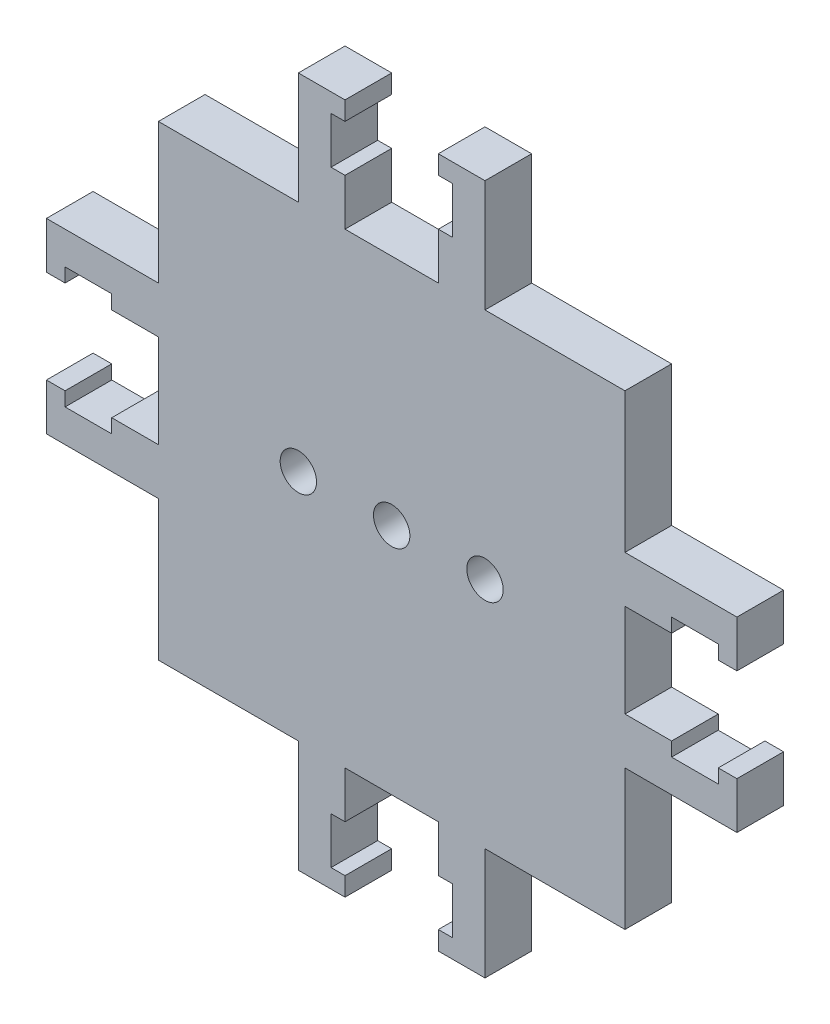
SolidWorks part; units mm, degrees
ref_plane "Plan de face" through (0, 0, 0) normal (0, 0, 1) x (1, 0, 0)
ref_plane "Plan de dessus" through (0, 0, 0) normal (0, 1, 0) x (1, 0, 0)
ref_plane "Plan de droite" through (0, 0, 0) normal (1, 0, 0) x (0, 0, -1)
sketch "Esquisse1" plane through (0, 0, 0) normal (0, 0, 1) x (1, 0, 0)
  line L0 (0, -10.9037) -> (0, 0) construction
  line L1 (0, 0) -> (78.1485, 0) construction
  line L2 (-25, 25) -> (-10, 25)
  line L3 (0, 0) -> (90.4553, 90.4553) construction
  line L4 (10, 25) -> (25, 25)
  line L5 (-25, -25) -> (-10, -25)
  line L6 (25, -25) -> (25, -10)
  line L8 (25, 10) -> (25, 25)
  line L9 (-25, -25) -> (-25, -10)
  line L10 (-25, 10) -> (-25, 25)
  line L13 (10, -25) -> (25, -25)
  circle A0 centre (0, 0) radius 1.95
  circle A1 centre (10, 0) radius 1.95
  circle A2 centre (-10, 0) radius 1.95
  line B0 (0, -25) -> (0, -13.135) construction
  line B1 (0, -25) -> (-5, -25)
  line B2 (-5, -30) -> (-10, -30) construction
  line B3 (-10, -30) -> (-10, -25)
  line B4 (-5, -30) -> (-5, -25)
  line B5 (0, -25) -> (5, -25)
  line B6 (5, -25) -> (5, -30)
  line B7 (5, -30) -> (10, -30) construction
  line B8 (10, -30) -> (10, -25)
  line B9 (-10, -30) -> (-10, -37)
  line B10 (-10, -37) -> (-5, -37)
  line B11 (-5, -37) -> (-5, -35)
  line B12 (-5, -35) -> (-6.5, -35)
  line B13 (-6.5, -35) -> (-6.5, -30)
  line B14 (-6.5, -30) -> (-5, -30)
  line B15 (5, -35) -> (6.5, -35)
  line B16 (10, -37) -> (5, -37)
  line B17 (5, -37) -> (5, -35)
  line B18 (6.5, -35) -> (6.5, -30)
  line B19 (10, -30) -> (10, -37)
  line B20 (10, -30) -> (10, -25)
  line B21 (5, -30) -> (6.5, -30)
  line B22 (0, -25) -> (0, -13.135) construction
  line B23 (0, -25) -> (5, -25)
  line B24 (5, -30) -> (10, -30) construction
  line B25 (10, -30) -> (10, -25)
  line B26 (5, -30) -> (5, -25)
  line B27 (0, -25) -> (-5, -25)
  line B28 (-5, -25) -> (-5, -30)
  line B29 (-5, -30) -> (-10, -30) construction
  line B30 (-10, -30) -> (-10, -25)
  line B31 (10, -30) -> (10, -37)
  line B32 (10, -37) -> (5, -37)
  line B33 (5, -37) -> (5, -35)
  line B34 (5, -35) -> (6.5, -35)
  line B35 (6.5, -35) -> (6.5, -30)
  line B36 (6.5, -30) -> (5, -30)
  line B37 (-5, -35) -> (-6.5, -35)
  line B38 (-10, -37) -> (-5, -37)
  line B39 (-5, -37) -> (-5, -35)
  line B40 (-6.5, -35) -> (-6.5, -30)
  line B41 (-10, -30) -> (-10, -37)
  line B42 (-10, -30) -> (-10, -25)
  line B43 (-5, -30) -> (-6.5, -30)
  line B44 (0, 25) -> (0, 13.135) construction
  line B45 (0, 25) -> (-5, 25)
  line B46 (-5, 30) -> (-10, 30) construction
  line B47 (-10, 30) -> (-10, 25)
  line B48 (-5, 30) -> (-5, 25)
  line B49 (0, 25) -> (5, 25)
  line B50 (5, 25) -> (5, 30)
  line B51 (5, 30) -> (10, 30) construction
  line B52 (10, 30) -> (10, 25)
  line B53 (-10, 30) -> (-10, 37)
  line B54 (-10, 37) -> (-5, 37)
  line B55 (-5, 37) -> (-5, 35)
  line B56 (-5, 35) -> (-6.5, 35)
  line B57 (-6.5, 35) -> (-6.5, 30)
  line B58 (-6.5, 30) -> (-5, 30)
  line B59 (5, 35) -> (6.5, 35)
  line B60 (10, 37) -> (5, 37)
  line B61 (5, 37) -> (5, 35)
  line B62 (6.5, 35) -> (6.5, 30)
  line B63 (10, 30) -> (10, 37)
  line B64 (10, 30) -> (10, 25)
  line B65 (5, 30) -> (6.5, 30)
  line B66 (25, 0) -> (13.135, 0) construction
  line B67 (25, 0) -> (25, -5)
  line B68 (30, -5) -> (30, -10) construction
  line B69 (30, -10) -> (25, -10)
  line B70 (30, -5) -> (25, -5)
  line B71 (25, 0) -> (25, 5)
  line B72 (25, 5) -> (30, 5)
  line B73 (30, 5) -> (30, 10) construction
  line B74 (30, 10) -> (25, 10)
  line B75 (30, -10) -> (37, -10)
  line B76 (37, -10) -> (37, -5)
  line B77 (37, -5) -> (35, -5)
  line B78 (35, -5) -> (35, -6.5)
  line B79 (35, -6.5) -> (30, -6.5)
  line B80 (30, -6.5) -> (30, -5)
  line B81 (35, 5) -> (35, 6.5)
  line B82 (37, 10) -> (37, 5)
  line B83 (37, 5) -> (35, 5)
  line B84 (35, 6.5) -> (30, 6.5)
  line B85 (30, 10) -> (37, 10)
  line B86 (30, 10) -> (25, 10)
  line B87 (30, 5) -> (30, 6.5)
  line B88 (-25, 0) -> (-13.135, 0) construction
  line B89 (-25, 0) -> (-25, -5)
  line B90 (-30, -5) -> (-30, -10) construction
  line B91 (-30, -10) -> (-25, -10)
  line B92 (-30, -5) -> (-25, -5)
  line B93 (-25, 0) -> (-25, 5)
  line B94 (-25, 5) -> (-30, 5)
  line B95 (-30, 5) -> (-30, 10) construction
  line B96 (-30, 10) -> (-25, 10)
  line B97 (-30, -10) -> (-37, -10)
  line B98 (-37, -10) -> (-37, -5)
  line B99 (-37, -5) -> (-35, -5)
  line B100 (-35, -5) -> (-35, -6.5)
  line B101 (-35, -6.5) -> (-30, -6.5)
  line B102 (-30, -6.5) -> (-30, -5)
  line B103 (-35, 5) -> (-35, 6.5)
  line B104 (-37, 10) -> (-37, 5)
  line B105 (-37, 5) -> (-35, 5)
  line B106 (-35, 6.5) -> (-30, 6.5)
  line B107 (-30, 10) -> (-37, 10)
  line B108 (-30, 10) -> (-25, 10)
  line B109 (-30, 5) -> (-30, 6.5)
  dimension "D11" = 3.9
  dimension "D4" = 3.9
  dimension "D2" = 50
  dimension "D3" = 50
  dimension "D5" = 45
  dimension "D6" = 10
sketch_block_instance "Insert plots ep 5mm avec ergots-1"
sketch_block "Insert plots ep 5mm avec ergots" parameters "D1"=10, "D2"=5, "D3"=5, "D4"=5, "D5"=2, "D6"=1.5, "D7"=2, "D8"=2, "D9"=2.0716, "D10"=2
sketch_block_instance "Insert plots ep 5mm avec ergots-3"
sketch_block_instance "Insert plots ep 5mm avec ergots-4"
sketch_block_instance "Insert plots ep 5mm avec ergots-6"
sketch_block_instance "Insert plots ep 5mm avec ergots-7"
extrude "Boss.-Extru.1" add sketch "Esquisse1" along normal blind 5 contours L4 B52 B63 B60 B61 B59 B62 B65 B50 B49 region at (-17.5, 23.9535, 0)
